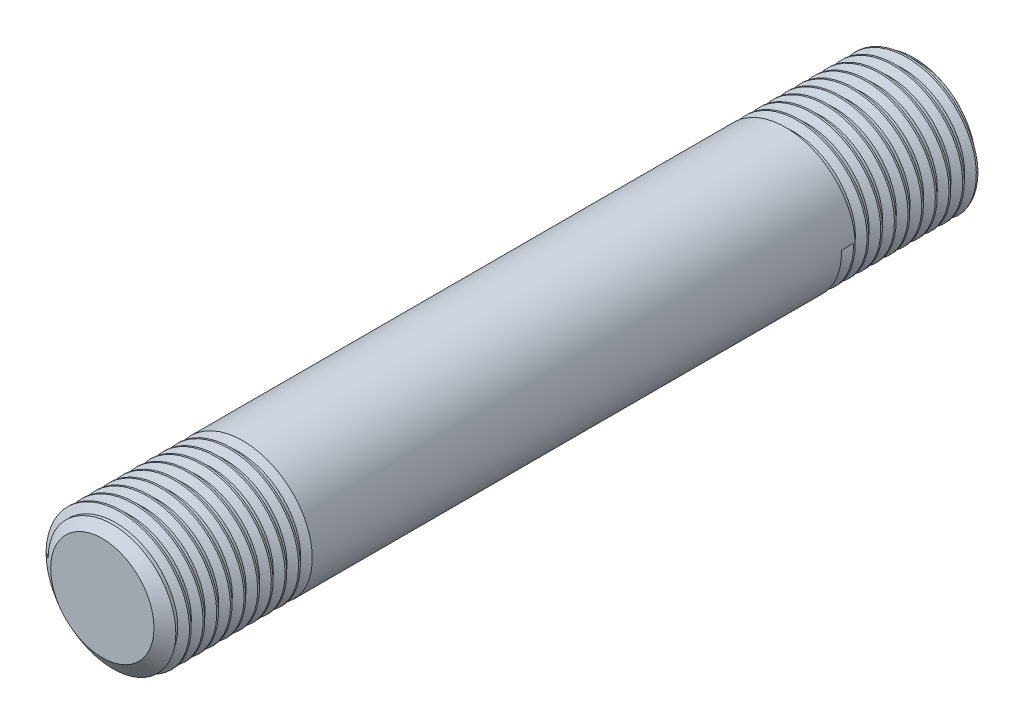
SolidWorks part; units mm, degrees
ref_plane "Спереди" through (0, 0, 0) normal (0, 0, 1) x (1, 0, 0)
ref_plane "Сверху" through (0, 0, 0) normal (0, 1, 0) x (1, 0, 0)
ref_plane "Справа" through (0, 0, 0) normal (1, 0, 0) x (0, 0, -1)
sketch "Эскиз1" plane through (0, 0, 0) normal (0, 0, 1) x (1, 0, 0)
  circle A0 centre (0, 0) radius 10
  dimension "D1" = 20
extrude "Бобышка-Вытянуть1" add sketch "Эскиз1" along normal mid plane 120
thread "Резьба1" pitch 2 method cut profile "Профиль резьбы1" start angle 0, offset 0, length 20, pitch 2, diameter 20
ref_plane "Плоскость4" through (10, 0, -60) normal (0, -1, 0) x (1, 0, 0)
sketch "Профиль резьбы1" plane through (10, 0, -60) normal (0, -1, 0) x (1, 0, 0)
  line L0 (0, 0) -> (0, 2) construction
  line L11 (0, 0) -> (0, 1.75)
  line L12 (0, 1.75) -> (-1.0825, 1.125)
  line L13 (-1.0825, 1.125) -> (-1.0825, 0.625)
  line L15 (-1.0825, 0.625) -> (0, 0)
  line L17 (-1.0825, 0.875) -> (0, 0.875) construction
  point P2 (0, 0)
  dimension "Pitch" = 2
  dimension "Profile_Angle" = 60
  dimension "Profile_Land" = 0.5
  dimension "Profile_Height" = 1.0825
thread "Резьба2" pitch 2 method cut profile "Профиль резьбы2" start angle 0, offset 0, length 20, pitch 2, diameter 20
ref_plane "Плоскость5" through (-10, 0, 60) normal (0, -1, 0) x (-1, 0, 0)
sketch "Профиль резьбы2" plane through (-10, 0, 60) normal (0, -1, 0) x (-1, 0, 0)
  line L0 (0, 0) -> (0, 2) construction
  line L11 (0, 0) -> (0, 1.75)
  line L12 (0, 1.75) -> (-1.0825, 1.125)
  line L13 (-1.0825, 1.125) -> (-1.0825, 0.625)
  line L15 (-1.0825, 0.625) -> (0, 0)
  line L17 (-1.0825, 0.875) -> (0, 0.875) construction
  point P2 (0, 0)
  dimension "Pitch" = 2
  dimension "Profile_Angle" = 60
  dimension "Profile_Land" = 0.5
  dimension "Profile_Height" = 1.0825
sketch "Эскиз8" plane through (0, 0, 0) normal (0, 1, 0) x (1, 0, 0)
  line L1 (10, 60) -> (10, 58.25)
  line L2 (10, 58.25) -> (7.5633, 60)
  line L3 (7.5633, 60) -> (10, 60)
  line L4 (-10, -58.25) -> (-10, -60)
  line L5 (-10, -58.25) -> (-7.5633, -60)
  line L6 (-10, -60) -> (10, -60) construction
  line L7 (-7.5633, -60) -> (-10, -60)
  line L8 (10, 60) -> (-10, 60) construction
  line L9 (0, -1000) -> (0, 49000) construction
  dimension "D1" = 3
  dimension "D2" = 3
revolve "Вырез-Повернуть1" cut sketch "Эскиз8" angle 360 about L9
